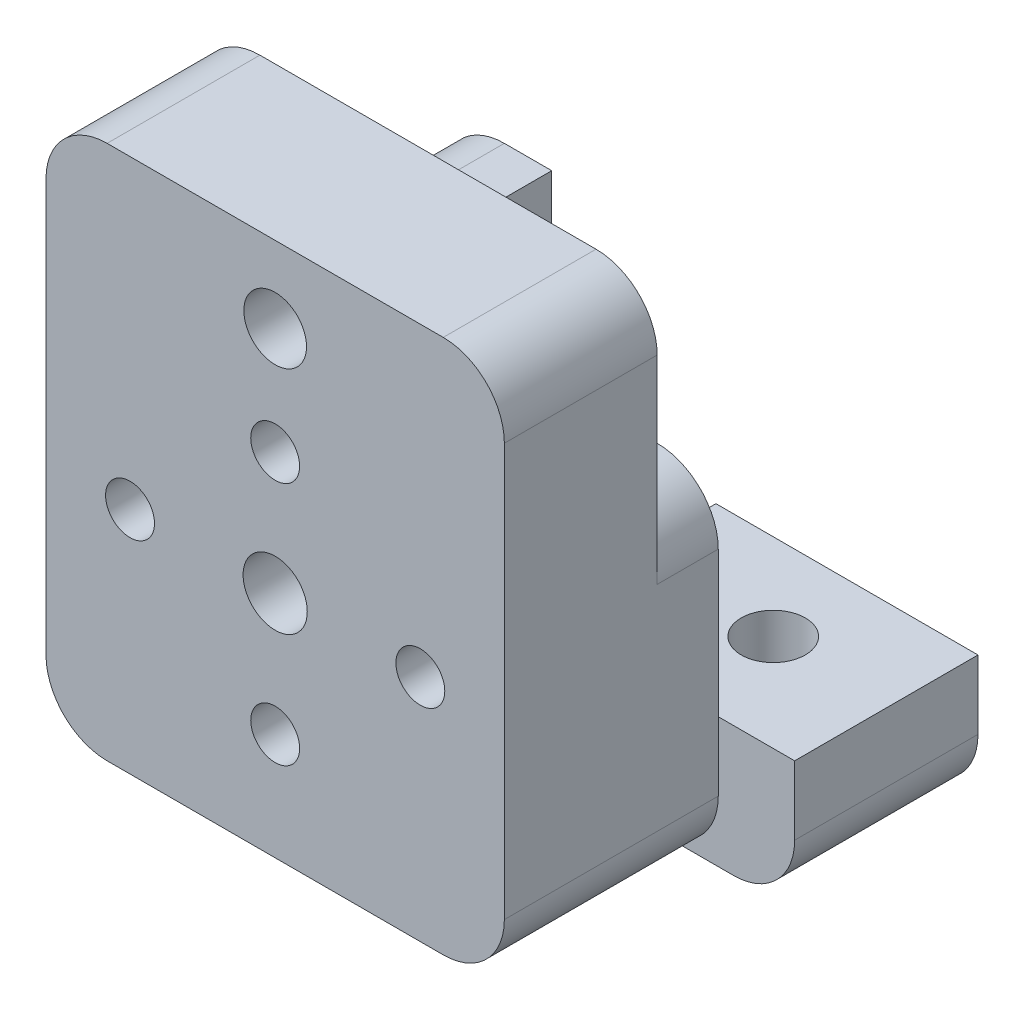
SolidWorks part; units mm, degrees
ref_plane "Front Plane" through (0, 0, 0) normal (0, 0, 1) x (1, 0, 0)
ref_plane "Top Plane" through (0, 0, 0) normal (0, 1, 0) x (1, 0, 0)
ref_plane "Right Plane" through (0, 0, 0) normal (1, 0, 0) x (0, 0, -1)
sketch "Sketch1" plane through (0, 0, 0) normal (0, 0, 1) x (1, 0, 0)
  line L0 (5.5, 15) -> (24.5, 15) construction
  line L1 (0, 0) -> (30, 0)
  line L2 (0, 0) -> (0, 35)
  line L3 (0, 35) -> (30, 35)
  line L4 (30, 0) -> (30, 35)
  line L5 (15, 7) -> (15, 23) construction
  circle A0 centre (15, 30) radius 2.05
  circle A1 centre (15, 15) radius 2.1
  circle A2 centre (5.5, 15) radius 1.6
  circle A3 centre (24.5, 15) radius 1.6
  circle A4 centre (15, 7) radius 1.6
  circle A5 centre (15, 23) radius 1.6
  point P10 (15, 0)
  point P14 (15, 15)
  point P18 (15, 15)
  dimension "D3" = 4.1
  dimension "D4" = 4.2
  dimension "D10" = 3.2
  dimension "D1" = 35
  dimension "D2" = 30
  dimension "D5" = 15
  dimension "D6" = 5
  dimension "D8" = 19
  dimension "D9" = 16
extrude "Boss-Extrude1" add sketch "Sketch1" along normal blind 10
sketch "Sketch2" plane through (0, 0, 0) normal (0, 0, -1) x (-1, 0, 0)
  circle A0 centre (-15, 7) radius 2.85
  circle A1 centre (-24.5, 15) radius 2.85
  circle A2 centre (-15, 23) radius 2.85
  circle A3 centre (-5.5, 15) radius 2.85
  circle A4 centre (-15, 7) radius 1.6 construction
  circle A5 centre (-24.5, 15) radius 1.6 construction
  circle A6 centre (-5.5, 15) radius 1.6 construction
  circle A7 centre (-15, 23) radius 1.6 construction
  dimension "D1" = 5.7
extrude "Cut-Extrude1" cut sketch "Sketch2" against normal blind 5
sketch "Sketch3" plane through (0, 0, 10) normal (0, 0, 1) x (1, 0, 0)
  circle A0 centre (15, 15) radius 3.65
  circle A1 centre (15, 30) radius 3.65
  circle A2 centre (15, 30) radius 2.05 construction
  circle A3 centre (15, 15) radius 2.1 construction
  dimension "D1" = 7.3
extrude "Cut-Extrude2" [suppressed] cut sketch "Sketch3" against normal blind 7
fillet "Fillet1" radius 4 4 edges at (0, 35, 5) (30, 35, 5) (30, 0, 5) (0, 0, 5)
sketch "Sketch5" [suppressed] plane through (0, 0, 10) normal (0, 0, 1) x (1, 0, 0)
  line L4 (6.5, 32.5) -> (6.5, 23.4706)
  line L5 (6.5, 23.4706) -> (4.2071, 21.1777)
  line L6 (4.2071, 8.8223) -> (8.8223, 4.2071)
  line L7 (2.5, 8.1152) -> (2.5, 4)
  line L8 (27.5, 4) -> (27.5, 31)
  line L9 (4, 2.5) -> (26, 2.5)
  line L10 (2.5, 31) -> (2.5, 4)
  line L11 (26, 32.5) -> (4, 32.5)
  line L13 (4, 2.5) -> (8.1152, 2.5)
  line L14 (2.5, 31) -> (2.5, 21.8848)
  line L15 (6.5, 32.5) -> (4, 32.5)
  line L16 (15, 15) -> (15, 30) construction
  line L17 (26, 2.5) -> (21.8848, 2.5)
  line L18 (27.5, 8.1152) -> (27.5, 4)
  line L19 (23.5, 32.5) -> (26, 32.5)
  line L20 (27.5, 31) -> (27.5, 21.8848)
  line L21 (25.7929, 8.8223) -> (21.1777, 4.2071)
  line L22 (23.5, 23.4706) -> (25.7929, 21.1777)
  line L23 (23.5, 32.5) -> (23.5, 23.4706)
  circle A4 centre (15, 15) radius 2.1 construction
  arc A5 (4.2071, 8.8223) -> (2.5, 8.1152) centre (3.5, 8.1152) ccw
  arc A6 (8.8223, 4.2071) -> (8.1152, 2.5) centre (8.1152, 3.5) cw
  arc A7 (4.2071, 21.1777) -> (2.5, 21.8848) centre (3.5, 21.8848) cw
  circle A8 centre (15, 15) radius 3.65 construction
  arc A9 (27.5, 31) -> (26, 32.5) centre (26, 31) ccw
  arc A11 (26, 2.5) -> (27.5, 4) centre (26, 4) ccw
  arc A17 (2.5, 4) -> (4, 2.5) centre (4, 4) ccw
  arc A18 (2.5, 4) -> (4, 2.5) centre (4, 4) ccw
  arc A19 (4, 32.5) -> (2.5, 31) centre (4, 31) ccw
  arc A20 (4, 32.5) -> (2.5, 31) centre (4, 31) ccw
  circle A21 centre (15, 30) radius 3.65 construction
  arc A22 (27.5, 4) -> (26, 2.5) centre (26, 4) cw
  arc A23 (26, 32.5) -> (27.5, 31) centre (26, 31) cw
  arc A24 (25.7929, 21.1777) -> (27.5, 21.8848) centre (26.5, 21.8848) ccw
  arc A25 (21.1777, 4.2071) -> (21.8848, 2.5) centre (21.8848, 3.5) ccw
  arc A26 (25.7929, 8.8223) -> (27.5, 8.1152) centre (26.5, 8.1152) cw
  point P13 (2.5, 10.5294)
  point P37 (27.5, 10.5294)
  dimension "D6" = 12
  dimension "D7" = 1
  dimension "D2" = 45
  dimension "D3" = 45
  dimension "D4" = 4
  dimension "D5" = 12
  dimension "D1" = 2.5
extrude "Cut-Extrude3" [suppressed] cut sketch "Sketch5" against normal through all
sketch "Sketch6" plane through (0, 0, 0) normal (0, 0, 1) x (1, 0, 0)
  line L0 (26, 22) -> (17.6688, 22)
  line L1 (4, 0) -> (26, 0) construction
  line L2 (12.3312, 22) -> (4, 22)
  line L4 (26, 35) -> (4, 35)
  line L5 (0, 31) -> (0, 4)
  line L6 (4, 0) -> (26, 0)
  line L7 (30, 4) -> (30, 31)
  line L9 (0, 18) -> (0, 4)
  line L10 (4, 0) -> (26, 0)
  line L11 (30, 4) -> (30, 18)
  arc A0 (26, 22) -> (30, 18) centre (26, 18) cw
  arc A1 (4, 22) -> (0, 18) centre (4, 18) ccw
  circle A2 centre (5.5, 15) radius 2.85 construction
  circle A3 centre (15, 7) radius 2.85 construction
  arc A4 (4, 35) -> (0, 31) centre (4, 31) ccw
  arc A5 (0, 4) -> (4, 0) centre (4, 4) ccw
  arc A6 (26, 0) -> (30, 4) centre (26, 4) ccw
  arc A7 (30, 31) -> (26, 35) centre (26, 31) ccw
  arc A9 (0, 4) -> (4, 0) centre (4, 4) ccw
  arc A10 (26, 0) -> (30, 4) centre (26, 4) ccw
  circle A12 centre (24.5, 15) radius 2.85 construction
  circle A13 centre (5.5, 15) radius 2.85
  circle A14 centre (15, 7) radius 2.85
  circle A15 centre (24.5, 15) radius 2.85
  circle A16 centre (15, 23) radius 2.85 construction
  arc A17 (12.3312, 22) -> (17.6688, 22) centre (15, 23) ccw
  dimension "D3" = 4
  dimension "D2" = 22
  dimension "D1" = 0
extrude "Boss-Extrude2" add sketch "Sketch6" against normal blind 4
ref_axis "Axis1" through (15, 15, 10) along (0, 0, -1)
sketch "Sketch7" plane through (0, 0, -4) normal (0, 0, -1) x (-1, 0, 0)
  line L0 (-30, 4) -> (-30, 18) construction
  line L2 (-7.1, 22) -> (-7.1, 17.85)
  line L3 (-7.1, 8.5) -> (-12.15, 8.5)
  line L5 (-4, 0) -> (-26, 0) construction
  line L6 (0, 18) -> (0, 4) construction
  line L7 (-12.3312, 22) -> (-4, 22) construction
  line L9 (-4, 0) -> (-26, 0)
  line L10 (0, 18) -> (0, 4)
  line L11 (-7.1, 22) -> (-4, 22)
  line L12 (-7.1, 12.15) -> (-7.1, 8.5)
  line L13 (-17.85, 8.5) -> (-30, 8.5)
  line L14 (-26, 0) -> (-31, 0)
  line L15 (-35, 4) -> (-35, 8.5)
  line L17 (-30, 8.5) -> (-35, 8.5)
  line L18 (-12.15, 7) -> (-12.15, 8.5)
  line L19 (-17.85, 7) -> (-17.85, 8.5)
  line L20 (-5.5, 12.15) -> (-7.1, 12.15)
  line L21 (-5.5, 17.85) -> (-7.1, 17.85)
  arc A1 (-4, 0) -> (0, 4) centre (-4, 4) ccw construction
  arc A2 (0, 18) -> (-4, 22) centre (-4, 18) ccw construction
  arc A4 (-4, 0) -> (0, 4) centre (-4, 4) ccw
  arc A5 (0, 18) -> (-4, 22) centre (-4, 18) ccw
  circle A6 centre (-5.5, 15) radius 2.85 construction
  circle A7 centre (-15, 7) radius 2.85 construction
  arc A8 (-5.5, 12.15) -> (-5.5, 17.85) centre (-5.5, 15) ccw
  arc A9 (-17.85, 7) -> (-12.15, 7) centre (-15, 7) ccw
  arc A10 (-31, 0) -> (-35, 4) centre (-31, 4) cw
  dimension "D1" = 8.5
  dimension "D2" = 7.1
  dimension "D3" = 5
extrude "Boss-Extrude3" add sketch "Sketch7" along normal blind 12
sketch "Sketch8" plane through (0, 0, 0) normal (0, -1, 0) x (1, 0, 0)
  circle A0 centre (27.2494, -10.35) radius 1.65 construction
  circle A1 centre (12.2494, -10.35) radius 1.65 construction
  circle A6 centre (27.2494, -10.35) radius 1.65 construction
  circle A7 centre (12.2494, -10.35) radius 1.65 construction
  circle A8 centre (12.2494, -10.35) radius 2.1
  circle A9 centre (27.2494, -10.35) radius 2.1
  dimension "D1" = 4.2
extrude "Cut-Extrude4" cut sketch "Sketch8" against normal through all
